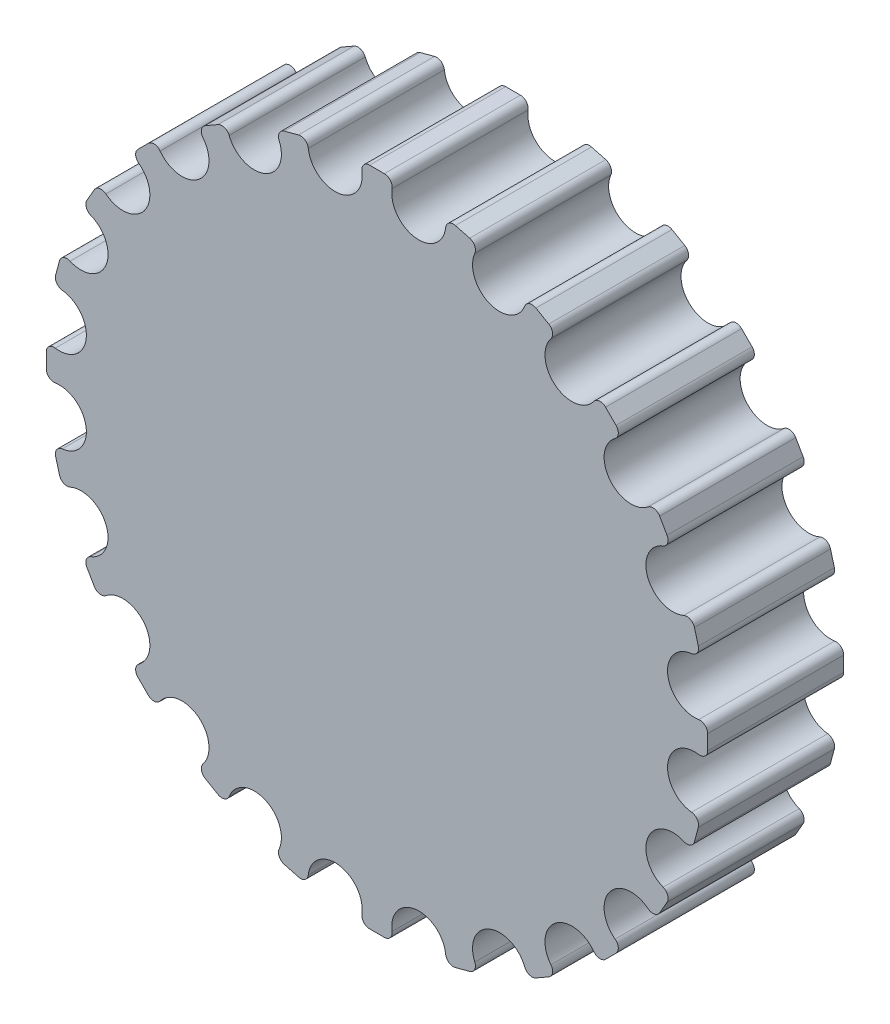
SolidWorks part; units mm, degrees
material "PE High Density"
ref_plane "Front Plane" through (0, 0, 0) normal (0, 0, 1) x (1, 0, 0)
ref_plane "Top Plane" through (0, 0, 0) normal (0, 1, 0) x (1, 0, 0)
ref_plane "Right Plane" through (0, 0, 0) normal (1, 0, 0) x (0, 0, -1)
sketch "PD" plane through (0, 0, 0) normal (0, 0, 1) x (1, 0, 0)
  circle A0 centre (0, 0) radius 19.0986
  dimension "PD" = 38.1972
extrude "half width" add sketch "PD" along normal blind 7.5
sketch "Sketch3" plane through (0, 0, 7.5) normal (0, 0, 1) x (1, 0, 0)
  line L0 (0, 0) -> (0, 18.2286) construction
  line L1 (0, 18.2286) -> (0.4071, 18.2286)
  line L2 (0, 0) -> (2.3049, 17.5075) construction
  line L3 (0, 18.2286) -> (0, 19.0986)
  line L4 (4.7179, 17.6075) -> (4.9431, 18.4478)
  line L5 (4.7179, 17.6075) -> (4.3247, 17.7128)
  line L6 (2.3049, 17.5075) -> (2.4929, 18.9352) construction
  arc A0 (0.4071, 18.2286) -> (0.8321, 17.7334) centre (0.4071, 17.7986) cw
  arc A1 (0.8321, 17.7334) -> (3.786, 17.3445) centre (2.3049, 17.5075) ccw
  circle A2 centre (0, 0) radius 19.0986 construction
  arc A3 (0, 19.0986) -> (4.9431, 18.4478) centre (0, 0) cw
  arc A4 (4.3247, 17.7128) -> (3.786, 17.3445) centre (4.2134, 17.2975) ccw
  point P8 (2.1104, 16.0303)
  dimension "D1" = 0.43
  dimension "D2" = 1.49
  dimension "D5" = 2.93
  dimension "D3" = 0.87
  dimension "D4" = 7.5
extrude "Teeth " cut sketch "Sketch3" against normal up to surface (7.5 mm away) up to face at (19.0986, 0, 0)
pattern_circular "CirPattern1" count 24 over 360 about axis through (0, 0, 7.5) along (0, 0, 1) of "Teeth "
equation "\"n\"=24"
equation "\"p\"= 5'pitch"
equation "\"pd\"= \"n\" * \"p\" / pi'pitch diameter"
equation "\"PD@PD\"=\"pd\""
equation "\"D1@CirPattern1\"=\"n\""
equation "\"D1@Sketch4\"= \"pd\" + 5"
equation "\"Bolt diameter\"= 3mm"
equation "\"D1@Sketch6\"= \"Bolt diameter\""
